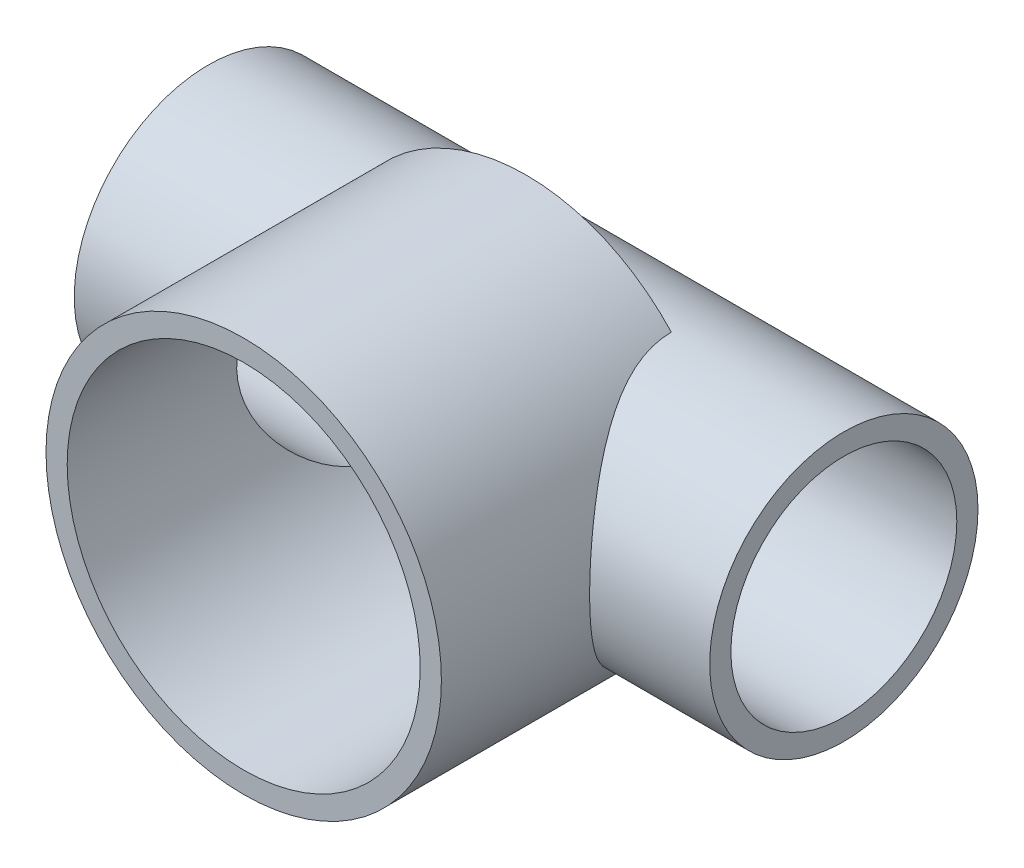
SolidWorks part; units mm, degrees
material "ABS"
ref_plane "前视基准面" through (0, 0, 0) normal (0, 0, 1) x (1, 0, 0)
ref_plane "上视基准面" through (0, 0, 0) normal (0, 1, 0) x (1, 0, 0)
ref_plane "右视基准面" through (0, 0, 0) normal (1, 0, 0) x (0, 0, -1)
sketch "草图1" plane through (0, 0, 0) normal (0, 0, 1) x (1, 0, 0)
  circle A0 centre (0, 0) radius 14
  circle A1 centre (0, 0) radius 12.5
  dimension "D1" = 25
  dimension "D2" = 1.5
extrude "凸台-拉伸1" add sketch "草图1" along normal blind 20
sketch "草图2" plane through (0, 0, 0) normal (1, 0, 0) x (0, 0, -1)
  circle A0 centre (0, 0) radius 8
  circle A1 centre (0, 0) radius 9.5
  dimension "D1" = 16
  dimension "D2" = 1.5
extrude "凸台-拉伸2" add sketch "草图2" along normal blind 22.5 and the other way blind 22.5
sketch "草图3" plane through (0, 0, 20) normal (0, 0, 1) x (1, 0, 0)
  circle A0 centre (0, 0) radius 12.5
extrude "切除-拉伸1" cut sketch "草图3" against normal blind 20 and the other way through all
sketch "草图4" plane through (22.5, 0, 0) normal (1, 0, 0) x (0, 0, -1)
  circle A0 centre (0, 0) radius 8
extrude "切除-拉伸2" cut sketch "草图4" against normal through all both and the other way through all
